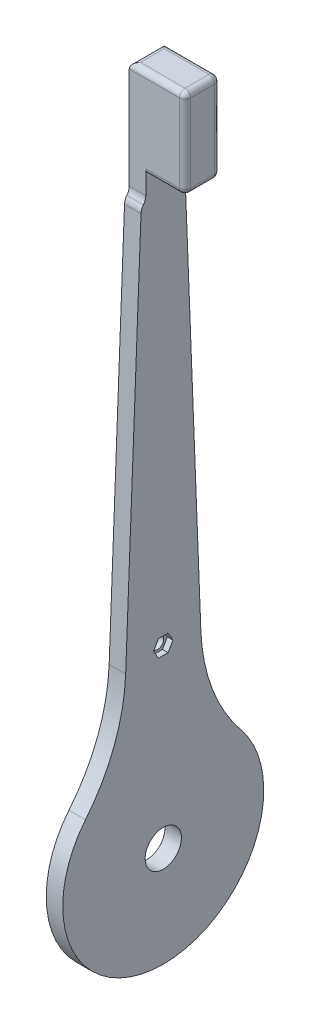
SolidWorks part; units mm, degrees
material "ABS"
ref_plane "Front Plane" through (0, 0, 0) normal (0, 0, 1) x (1, 0, 0)
ref_plane "Top Plane" through (0, 0, 0) normal (0, 1, 0) x (1, 0, 0)
ref_plane "Right Plane" through (0, 0, 0) normal (1, 0, 0) x (0, 0, -1)
sketch "Sketch2" plane through (0, 0, 0) normal (1, 0, 0) x (0, 0, -1)
  line L0 (4.9771, 193.675) -> (11.5599, 26.1323)
  line L1 (0, 193.675) -> (0, 28.575) construction
  line L2 (-4.9771, 193.675) -> (-11.5599, 26.1323)
  line L4 (-4.9771, 193.675) -> (4.9771, 193.675)
  circle A0 centre (0, 0) radius 28.575
  circle A1 centre (0, 0) radius 11.1125
  dimension "D1" = 57.15
  dimension "D5" = 22.225
  dimension "D2" = 11.5599
  dimension "D3" = 2.25
  dimension "D4" = 165.1
extrude "Boss-Extrude1" add sketch "Sketch2" against normal blind 6.35 contours A0 A1 region at (0, 15.1508, -23.269)
extrude "Boss-Extrude2" add sketch "Sketch2<5>" along normal blind 3.175 and the other way blind 1.524 contours L4 L1 A0 L0 | L1 L4 L2 A0 region at (0, 99.7845, -4.3525) region at (0, 99.7845, 4.3525)
sketch "Sketch2<5>" plane through (0, 0, 0) normal (1, 0, 0) x (0, 0, -1) same geometry as "Sketch2"
sketch "Sketch3" plane through (3.175, 0, 0) normal (1, 0, 0) x (0, 0, -1)
  line L0 (-4.9771, 193.675) -> (-4.9771, 168.275)
  line L1 (-4.9771, 168.275) -> (4.9771, 168.275)
  line L2 (4.9771, 168.275) -> (4.9771, 193.675)
  line L3 (-4.9771, 193.675) -> (4.9771, 193.675)
  dimension "D1" = 25.4
extrude "Boss-Extrude3" add sketch "Sketch3" along normal blind 11.176
sketch "Sketch4" plane through (3.175, 0, 0) normal (1, 0, 0) x (0, 0, -1)
  line L0 (-4.9771, 193.675) -> (-4.9771, 161.925)
  line L1 (-4.9771, 161.925) -> (-6.2246, 161.925)
  line L2 (-6.2246, 161.925) -> (-6.2246, 193.675)
  line L3 (-6.2246, 193.675) -> (-4.9771, 193.675)
  line L4 (-4.9771, 193.675) -> (-4.9086, 193.5806)
  line L5 (-4.9771, 193.675) -> (-11.5599, 26.1323) construction
  line L7 (0, 193.675) -> (0, 168.275) construction
  line L8 (-4.9771, 193.675) -> (4.9771, 193.675) construction
  line L9 (-4.9771, 168.275) -> (4.9771, 168.275) construction
  line L10 (4.9771, 193.675) -> (4.9086, 193.5806)
  line L11 (6.2246, 193.675) -> (4.9771, 193.675)
  line L12 (6.2246, 161.925) -> (6.2246, 193.675)
  line L13 (4.9771, 161.925) -> (6.2246, 161.925)
  line L14 (4.9771, 193.675) -> (4.9771, 161.925)
  line L15 (-4.9771, 168.275) -> (4.9771, 168.275) construction
  line M2 (4.9771, 193.675) -> (4.9771, 168.275)
  line M4 (-4.9771, 168.275) -> (-4.9771, 193.675)
  line M5 (-4.9771, 193.675) -> (-11.5599, 26.1323)
  line M7 (11.5599, 26.1323) -> (4.9771, 193.675)
  dimension "D1" = 6.35
extrude "Cut-Extrude1" cut sketch "Sketch4" against normal through all contours L1 M4 M5 | L13 M2 M7 region at (3.175, 172.5083, 5.3929) region at (3.175, 172.5083, -5.3929)
fillet "Fillet2" radius 3.175 2 edges at (0.8255, 161.925, 6.2246) (0.8255, 161.925, -6.2246)
fillet "Fillet4" radius 3.175 2 edges at (0.8255, 161.925, 4.9771) (0.8255, 161.925, -4.9771)
fillet "Fillet7" radius 1.5875 9 edges at (8.763, 168.275, 4.9771) (8.763, 168.275, -4.9771) (14.351, 180.975, -4.9771) (6.4135, 193.675, 4.9771) (14.351, 180.975, 4.9771) (-1.524, 193.675, 0) (14.351, 193.675, 0) (14.351, 168.275, 0) (6.4135, 193.675, -4.9771)
sketch "Sketch5" plane through (0, 0, 0) normal (1, 0, 0) x (0, 0, -1)
  circle A1 centre (0, 0) radius 28.575
  dimension "D1" = 57.15
extrude "Cut-Extrude2" cut sketch "Sketch5" against normal through all
sketch "Sketch6" plane through (3.175, 0, 0) normal (1, 0, 0) x (0, 0, -1)
  circle A0 centre (0, 0) radius 28.575
  arc A1 (11.5599, 26.1323) -> (-11.5599, 26.1323) centre (0, 0) ccw construction
extrude "Boss-Extrude4" add sketch "Sketch6" against normal up to surface (4.699 mm away) up to face at (-1.524, 140.683, 0)
hole_wizard "3/8 Clearance Hole1" positions "Sketch8" profile "Sketch7" hole size "3/8" standard "ANSI Inch" end condition through all
sketch "Sketch8" plane through (3.175, 0, 0) normal (1, 0, 0) x (0, 0, -1)
  point P0 (0, 0)
sketch "Sketch7" plane through (3.175, 0, 0) normal (0, 1, 0) x (0, 0, -1)
  line L0 (0, 0) -> (0, 4.699)
  line L1 (0, 4.699) -> (5.1587, 4.699)
  line L2 (5.1587, 4.699) -> (5.1587, 0)
  line L5 (5.1587, 0) -> (0, 0)
  line L11 (0, -6.35) -> (0, 107.95) construction
  dimension "Thru Hole Dia." = 10.3175
  dimension "Thru Hole Depth" = 4.699
fillet "Fillet9" radius 50.8 2 edges at (0.8255, 26.1323, 11.5599) (0.8255, 26.1323, -11.5599)
hole_wizard "#4 Clearance Hole1" positions "Sketch10" profile "Sketch9" hole size "#4" standard "ANSI Inch" end condition through all
sketch "Sketch10" plane through (3.175, 0, 0) normal (1, 0, 0) x (0, 0, -1)
  line L0 (-10.6266, 49.8873) -> (10.6266, 49.8873) construction
  line L1 (-6.3217, 159.4537) -> (-10.6911, 48.2456) construction
  line L2 (6.3217, 159.4537) -> (10.6911, 48.2456) construction
  line L5 (3.3896, 192.0875) -> (-3.3896, 192.0875) construction
  line L6 (65.0064, 32.4689) -> (0, 49.8873) construction
  line L7 (59.9587, -55.5099) -> (-83.6938, -17.0183) construction
  point P0 (0, 49.8873)
sketch "Sketch9" plane through (3.175, 49.8873, 0) normal (0, 1, 0) x (0, 0, -1)
  line L0 (0, 0) -> (0, 4.699)
  line L1 (0, 4.699) -> (1.7272, 4.699)
  line L2 (1.7272, 4.699) -> (1.7272, 0)
  line L5 (1.7272, 0) -> (0, 0)
  line L11 (0, -6.35) -> (0, 107.95) construction
  dimension "Thru Hole Dia." = 3.4544
  dimension "Thru Hole Depth" = 4.699
sketch "Sketch11" plane through (3.175, 0, 0) normal (1, 0, 0) x (0, 0, -1)
  line L0 (-1.3823, 47.493) -> (1.3823, 47.493)
  line L1 (-1.2357, 47.747) -> (1.2357, 47.747) construction
  line L2 (1.2357, 47.747) -> (2.4714, 49.8873) construction
  line L3 (2.4714, 49.8873) -> (1.2357, 52.0276) construction
  line L4 (1.2357, 52.0276) -> (-1.2357, 52.0276) construction
  line L5 (-1.2357, 52.0276) -> (-2.4714, 49.8873) construction
  line L6 (-2.4714, 49.8873) -> (-1.2357, 47.747) construction
  line L7 (1.3823, 47.493) -> (2.7647, 49.8873)
  line L8 (2.7647, 49.8873) -> (1.3823, 52.2816)
  line L9 (1.3823, 52.2816) -> (-1.3823, 52.2816)
  line L10 (-1.3823, 52.2816) -> (-2.7647, 49.8873)
  line L11 (-2.7647, 49.8873) -> (-1.3823, 47.493)
  line L12 (3.3896, 192.0875) -> (-3.3896, 192.0875) construction
  circle A0 centre (0, 49.8873) radius 2.1403 construction
  dimension "D1" = 0.254
extrude "Cut-Extrude3" cut sketch "Sketch11" against normal blind 1.6002
